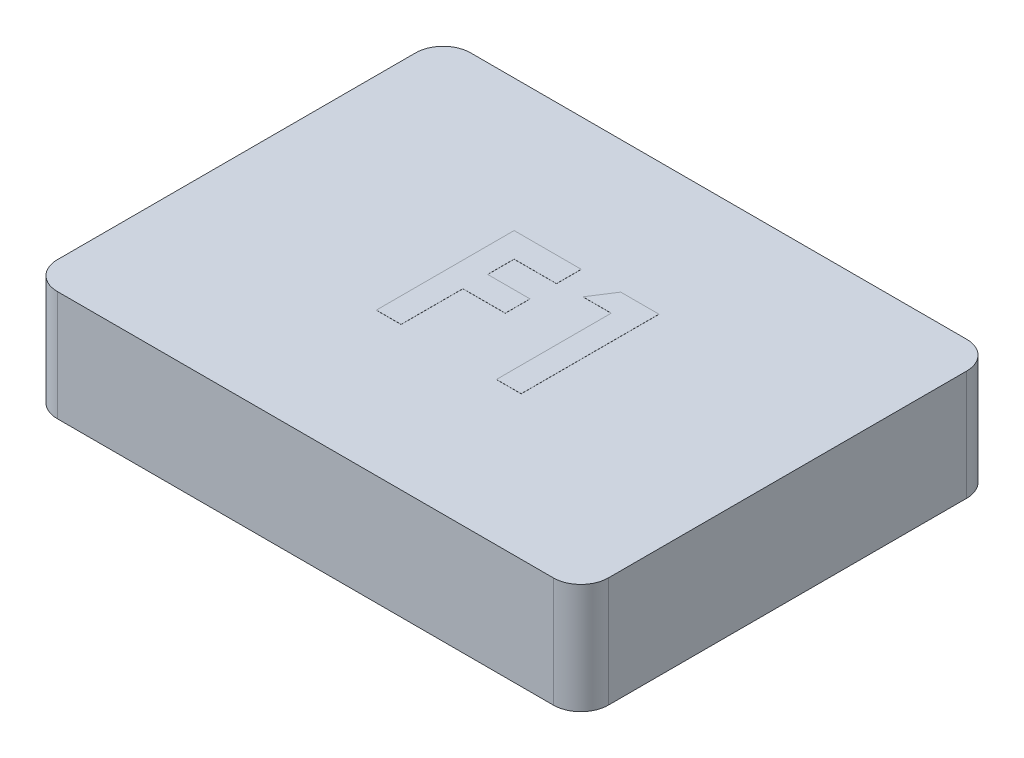
SolidWorks part; units mm, degrees
ref_plane "Front Plane" through (0, 0, 0) normal (0, 0, 1) x (1, 0, 0)
ref_plane "Top Plane" through (0, 0, 0) normal (0, 1, 0) x (1, 0, 0)
ref_plane "Right Plane" through (0, 0, 0) normal (1, 0, 0) x (0, 0, -1)
sketch "Sketch1" plane through (0, 0, 0) normal (0, 1, 0) x (1, 0, 0)
  line L0 (0, 0) -> (12.7, 0)
  line L1 (12.7, 0) -> (12.7, 9.525)
  line L2 (12.7, 9.525) -> (0, 9.525)
  line L3 (0, 9.525) -> (0, 0)
  dimension "D1" = 12.7
  dimension "D2" = 9.525
extrude "Boss-Extrude1" add sketch "Sketch1" along normal blind 2.54
fillet "Fillet1" radius 0.635 4 edges at (0, 1.27, -9.525) (12.7, 1.27, -9.525) (12.7, 1.27, 0) (0, 1.27, 0)
shell "Shell1" thickness 0.635 removed face at (6.35, 0, -4.7625)
sketch "Sketch2" plane through (0, 1.905, 0) normal (0, -1, 0) x (-1, 0, 0)
  line L0 (-0.635, 4.7625) -> (-12.065, 4.7625) construction
  line L1 (-0.635, 8.89) -> (-0.635, 0.635) construction
  line L2 (-12.065, 0.635) -> (-12.065, 8.89) construction
  line L3 (-6.35, 0.635) -> (-6.35, 8.89) construction
  line L4 (-0.635, 0.635) -> (-12.065, 0.635) construction
  line L5 (-12.065, 8.89) -> (-0.635, 8.89) construction
  circle A0 centre (-6.35, 4.7625) radius 2.54
  dimension "D1" = 5.08
extrude "Boss-Extrude2" add sketch "Sketch2" along normal up to surface (1.905 mm away) up to face at (6.35, 0, -4.7625)
sketch "Sketch3" plane through (0, 2.54, 0) normal (0, 1, 0) x (1, 0, 0)
  line L0 (0.635, 0) -> (12.065, 0) construction
  line L1 (0, 8.89) -> (0, 0.635) construction
  text T0 "<b>F1</b>"
  dimension "D1" = 3.302
  dimension "D2" = 4.318
extrude "Boss-Extrude3" add sketch "Sketch3" along normal blind 0.0025
